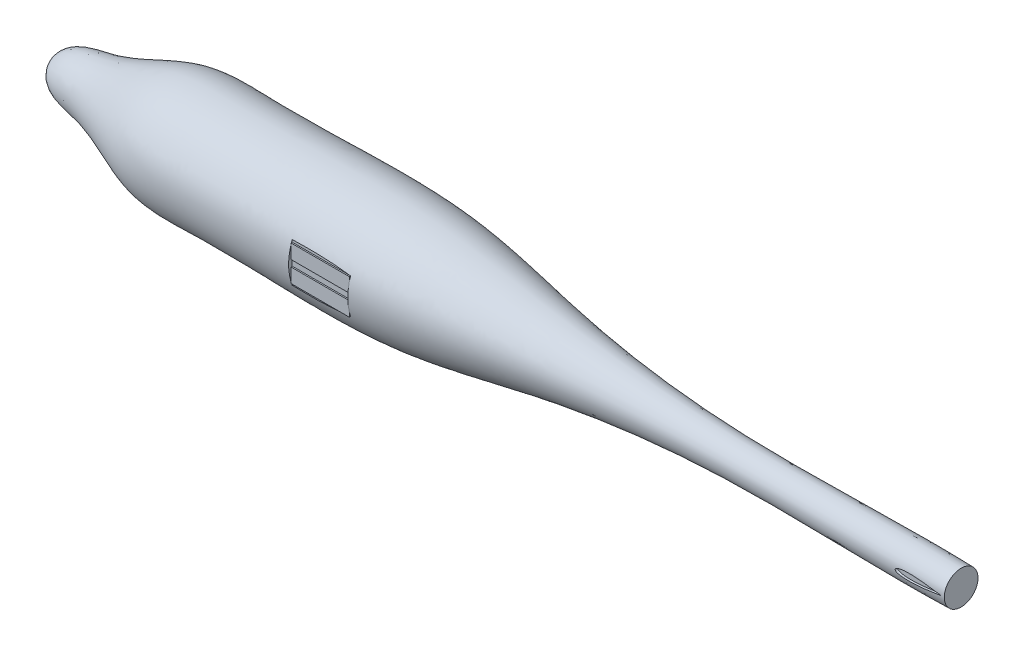
SolidWorks part; units mm, degrees
material "EPP"
ref_plane "Front Plane" through (0, 0, 0) normal (0, 0, 1) x (1, 0, 0)
ref_plane "Top Plane" through (0, 0, 0) normal (0, 1, 0) x (1, 0, 0)
ref_plane "Right Plane" through (0, 0, 0) normal (1, 0, 0) x (0, 0, -1)
sketch "Sketch1" plane through (0, 0, 0) normal (0, 0, 1) x (1, 0, 0)
  line L1 (1400, 97.6339) -> (0, 97.6339) construction
  line L3 (0, 0) -> (1400, 0) construction
  line L5 (0, 0) -> (1400, 0)
  line L6 (1400, 0) -> (1400, 25.997)
  spline S0 degree 3 poles (0, 0) (6.0079, 35.1205) (87.5704, 35.98) (174.2855, 89.8849) (355.2298, 80.4635) (551.199, 98.1903) (802.5668, 43.0656) (1072.4121, 17.7479) (1281.1497, 28.8593) (1400, 25.997) knots 0 0 0 0 0.060909 0.147322 0.213189 0.431417 0.561861 0.75012 1 1 1 1
  dimension "D1" = 97.6339
revolve "Revolve2" add sketch "Sketch1" angle 360 about L5
ref_plane "Plane1" through (0, 0, 88) normal (0, 0, 1) x (1, 0, 0)
sketch "Sketch5" plane through (0, 0, 88) normal (0, 0, 1) x (1, 0, 0)
  line L0 (0, 0) -> (1400, 0) construction
  line L1 (450, 100) -> (540, 100)
  line L2 (450, 100) -> (450, -100)
  line L3 (450, -100) -> (540, -100)
  line L4 (540, 100) -> (540, -100)
  line L5 (450, 100) -> (540, -100) construction
  line L6 (450, -100) -> (540, 100) construction
  line L7 (1400, -25.997) -> (1400, 25.997) construction
  point P0 (495, 0)
  dimension "D1" = 450
  dimension "D2" = 90
  dimension "D3" = 200
sketch "Sketch7" plane through (0, 0, 88) normal (0, 0, 1) x (1, 0, 0)
  line L1 (1330.1015, 25) -> (1400.1015, 25)
  line L2 (1330.1015, 25) -> (1330.1015, -25)
  line L3 (1330.1015, -25) -> (1400.1015, -25)
  line L4 (1400.1015, 25) -> (1400.1015, -25)
  line L5 (1330.1015, 25) -> (1400.1015, -25) construction
  line L6 (1330.1015, -25) -> (1400.1015, 25) construction
  point P0 (1365.1015, 0)
extrude "Cut-Extrude4" cut sketch "Sketch5" against normal blind 6.5
sketch "Sketch8" plane through (0, 0, 81.5) normal (0, 0, 1) x (1, 0, 0)
  line L0 (450, 0) -> (540, 0) construction
  line L1 (450, 30.5883) -> (450, -30.5883) construction
  line L2 (540, 27.0452) -> (540, -27.0452) construction
  line L3 (540, -27.0452) -> (540, 27.0452) construction
  line L4 (450, 5) -> (540, 5)
  line L5 (450, 5) -> (450, -5)
  line L6 (450, -5) -> (540, -5)
  line L7 (540, 5) -> (540, -5)
  line L8 (450, 5) -> (540, -5) construction
  line L9 (450, -5) -> (540, 5) construction
  line L11 (540, -27.0452) -> (450, -27.0452)
  line L12 (540, -27.0452) -> (540, -5)
  line L13 (540, -5) -> (450, -5)
  line L14 (450, -27.0452) -> (450, -5)
  line L15 (540, 27.0452) -> (450, 27.0452)
  line L16 (540, 27.0452) -> (540, 5)
  line L17 (540, 5) -> (450, 5)
  line L18 (450, 27.0452) -> (450, 5)
  point P6 (495, 0)
  line M2 (450, 30.5883) -> (450, -30.5883)
  line M4 (540, -27.0452) -> (540, 27.0452)
  dimension "D1" = 10
  dimension "D2" = 22.0452
extrude "Boss-Extrude1" add sketch "Sketch8" along normal blind 2 contours L15 L4 M4 M2 | L11 L6 M4 M2 region at (495, 16.0226, 81.5) region at (495, -16.0226, 81.5)
curve "Curve4"
  spline degree 3 poles (1395, 0.1106, 88) (1393.8337, 0.3112, 88) (1391.503, 0.7122, 88) (1386.8387, 1.4577, 88) (1381.0079, 2.3135, 88) (1374.0074, 3.2252, 88) (1367.0075, 4.0161, 88) (1360.0075, 4.6625, 88) (1353.0064, 5.1217, 88) (1347.1673, 5.2834, 88) (1342.498, 5.2197, 88) (1338.9941, 5.0466, 88) (1335.4854, 4.7134, 88) (1332.5643, 4.2469, 88) (1330.2314, 3.6922, 88) (1328.4601, 3.1359, 88) (1326.971, 2.4608, 88) (1325.6343, 1.5675, 88) (1324.5974, 0, 88) (1325.6343, -1.5675, 88) (1326.971, -2.4608, 88) (1328.4601, -3.1359, 88) (1330.2314, -3.6922, 88) (1332.5643, -4.2469, 88) (1335.4854, -4.7134, 88) (1338.9941, -5.0466, 88) (1342.498, -5.2197, 88) (1347.1673, -5.2834, 88) (1353.0064, -5.1217, 88) (1360.0075, -4.6625, 88) (1367.0075, -4.0161, 88) (1374.0074, -3.2252, 88) (1381.0079, -2.3135, 88) (1386.8387, -1.4577, 88) (1391.503, -0.7122, 88) (1393.8337, -0.3112, 88) (1395, -0.1106, 88) knots 0 0 0 0 0.024684 0.04933 0.098522 0.147602 0.196578 0.24545 0.294219 0.342904 0.367241 0.391608 0.416059 0.440726 0.453243 0.466028 0.479473 0.486972 0.5 0.513028 0.520527 0.533972 0.546757 0.559274 0.583941 0.608392 0.632759 0.657096 0.705781 0.75455 0.803422 0.852398 0.901478 0.95067 0.975316 1 1 1 1
sketch "Sketch14" plane through (0, 0, 88) normal (0, 0, 1) x (1, 0, 0)
  line L0 (1395, 0.1106) -> (1395, -0.1106)
  spline S0 degree 3 poles (1950.8551, 1916.4205) (1541.7499, -55.83) (1468.1035, -11.5304) (1386.8387, 1.4577) (1381.0079, 2.3135) (1374.0074, 3.2252) (1367.0075, 4.0161) (1360.0075, 4.6625) (1353.0064, 5.1217) (1347.1673, 5.2834) (1342.498, 5.2197) (1338.9941, 5.0466) (1335.4854, 4.7134) (1332.5643, 4.2469) (1330.2314, 3.6922) (1328.4601, 3.1359) (1326.971, 2.4608) (1325.6343, 1.5675) (1324.5974, 0) (1325.6343, -1.5675) (1326.971, -2.4608) (1328.4601, -3.1359) (1330.2314, -3.6922) (1332.5643, -4.2469) (1335.4854, -4.7134) (1338.9941, -5.0466) (1342.498, -5.2197) (1347.1673, -5.2834) (1353.0064, -5.1217) (1360.0075, -4.6625) (1367.0075, -4.0161) (1374.0074, -3.2252) (1381.0079, -2.3135) (1386.8387, -1.4577) (1468.103, 11.5303) (1541.749, 55.8295) (1950.8476, -1916.3842) knots -1.618016 -1.618016 -1.618016 -1.618016 0.024684 0.04933 0.098522 0.147602 0.196578 0.24545 0.294219 0.342904 0.367241 0.391608 0.416059 0.440726 0.453243 0.466028 0.479473 0.486972 0.5 0.513028 0.520527 0.533972 0.546757 0.559274 0.583941 0.608392 0.632759 0.657096 0.705781 0.75455 0.803422 0.852398 0.901478 0.95067 0.975316 2.618006 2.618006 2.618006 2.618006 only from (1395, 0.1106) to (1395, -0.1106) construction
  spline S1 degree 3 poles (1395, 0.1106) (1393.8337, 0.3112) (1391.503, 0.7122) (1386.8387, 1.4577) (1381.0079, 2.3135) (1374.0074, 3.2252) (1367.0075, 4.0161) (1360.0075, 4.6625) (1353.0064, 5.1217) (1347.1673, 5.2834) (1342.498, 5.2197) (1338.9941, 5.0466) (1335.4854, 4.7134) (1332.5643, 4.2469) (1330.2314, 3.6922) (1328.4601, 3.1359) (1326.971, 2.4608) (1325.6343, 1.5675) (1324.5974, 0) (1325.6343, -1.5675) (1326.971, -2.4608) (1328.4601, -3.1359) (1330.2314, -3.6922) (1332.5643, -4.2469) (1335.4854, -4.7134) (1338.9941, -5.0466) (1342.498, -5.2197) (1347.1673, -5.2834) (1353.0064, -5.1217) (1360.0075, -4.6625) (1367.0075, -4.0161) (1374.0074, -3.2252) (1381.0079, -2.3135) (1386.8387, -1.4577) (1391.503, -0.7122) (1393.8337, -0.3112) (1395, -0.1106) knots 0 0 0 0 0.024684 0.04933 0.098522 0.147602 0.196578 0.24545 0.294219 0.342904 0.367241 0.391608 0.416059 0.440726 0.453243 0.466028 0.479473 0.486972 0.5 0.513028 0.520527 0.533972 0.546757 0.559274 0.583941 0.608392 0.632759 0.657096 0.705781 0.75455 0.803422 0.852398 0.901478 0.95067 0.975316 1 1 1 1
extrude "Cut-Extrude7" cut sketch "Sketch14" against normal blind 65
